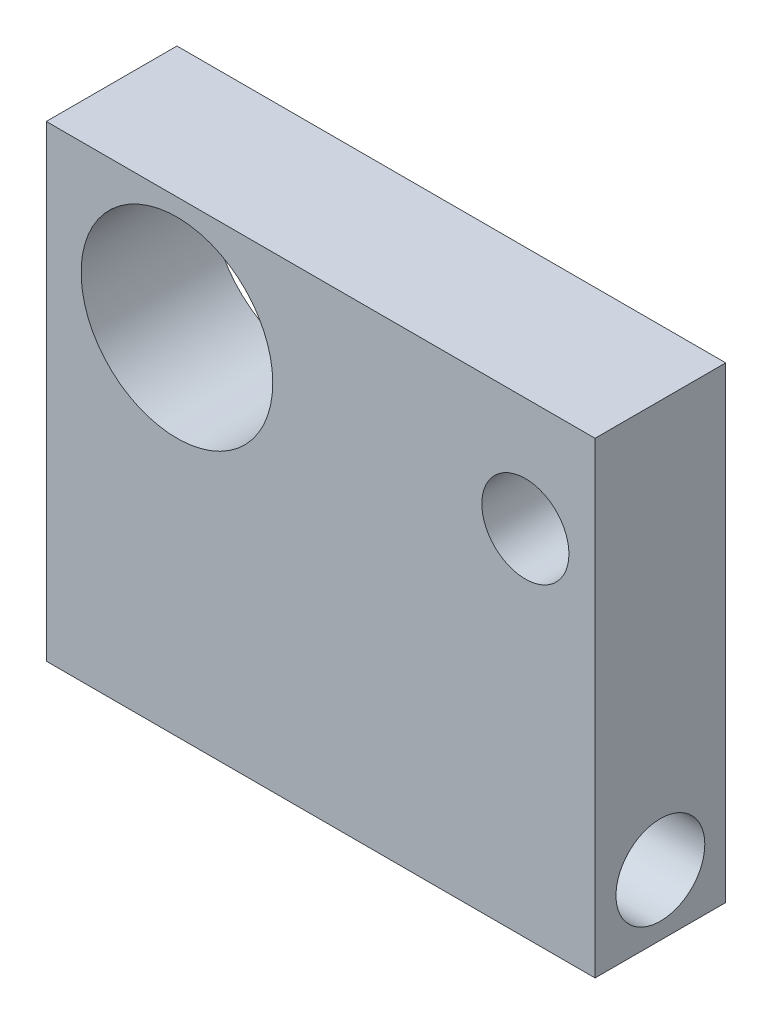
SolidWorks part; units mm, degrees
ref_plane "Front Plane" through (0, 0, 0) normal (0, 0, 1) x (1, 0, 0)
ref_plane "Top Plane" through (0, 0, 0) normal (0, 1, 0) x (1, 0, 0)
ref_plane "Right Plane" through (0, 0, 0) normal (1, 0, 0) x (0, 0, -1)
sketch "Sketch2" plane through (0, 0, 0) normal (0, 0, 1) x (1, 0, 0)
  line L1 (-31.9438, -27.208) -> (31.0562, -27.208)
  line L2 (-31.9438, -27.208) -> (-31.9438, 26.452)
  line L3 (-31.9438, 26.452) -> (31.0562, 26.452)
  line L4 (31.0562, -27.208) -> (31.0562, 26.452)
  line L5 (-31.9438, -27.208) -> (31.0562, 26.452) construction
  circle A0 centre (23.0562, 13.452) radius 5
  circle A1 centre (-16.9438, 13.452) radius 11
  point P0 (0, 0)
  point P10 (0, 0)
  point P11 (0, 0)
  dimension "D3" = 22
  dimension "D4" = 10
  dimension "D6" = 8
  dimension "D7" = 13
  dimension "D1" = 40.66
  dimension "D2" = 15
  dimension "D5" = 0
  dimension "D8" = 40
extrude "Boss-Extrude1" add sketch "Sketch2" along normal blind 15
sketch "Sketch3" plane through (31.0562, 0, 0) normal (1, 0, 0) x (0, 0, -1)
  line L0 (-15, -27.208) -> (0, -27.208) construction
  circle A0 centre (-7.5, -20.208) radius 5.1
  dimension "D1" = 10.2
  dimension "D2" = 7
extrude "Cut-Extrude1" cut sketch "Sketch3" against normal through all
